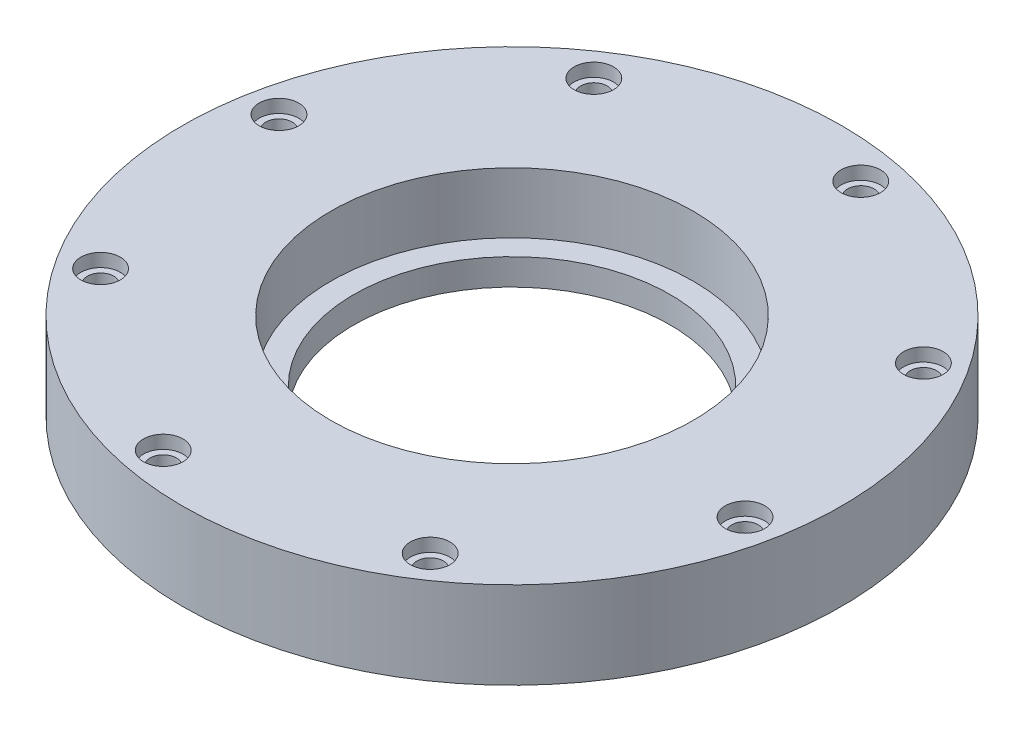
SolidWorks part; units mm, degrees
ref_plane "Front Plane" through (0, 0, 0) normal (0, 0, 1) x (1, 0, 0)
ref_plane "Top Plane" through (0, 0, 0) normal (0, 1, 0) x (1, 0, 0)
ref_plane "Right Plane" through (0, 0, 0) normal (1, 0, 0) x (0, 0, -1)
sketch "Sketch1" plane through (0, 0, 0) normal (0, 1, 0) x (1, 0, 0)
  circle A0 centre (0, 0) radius 24
  circle A1 centre (0, 0) radius 50
  dimension "D1" = 100
  dimension "D2" = 48
extrude "Boss-Extrude1" add sketch "Sketch1" along normal blind 13.2
sketch "Sketch2" plane through (0, 13.2, 0) normal (0, 1, 0) x (1, 0, 0)
  line L0 (0, 0) -> (24.7487, 24.7487)
  line L1 (0, 0) -> (32.3358, 13.3939)
  line L2 (24.7487, 24.7487) -> (32.3358, 13.3939)
  line L3 (0, 0) -> (28.5423, 19.0713)
  line L4 (28.5423, 19.0713) -> (37.4161, 25.0007)
  circle A0 centre (0, 0) radius 35
  circle A1 centre (0, 35) radius 3
  circle A2 centre (13.3939, 32.3358) radius 3
  circle A3 centre (24.7487, 24.7487) radius 3
  circle A4 centre (32.3358, 13.3939) radius 3
  circle A5 centre (35, 0) radius 3
  circle A6 centre (32.3358, -13.3939) radius 3
  circle A7 centre (24.7487, -24.7487) radius 3
  circle A8 centre (13.3939, -32.3358) radius 3
  circle A9 centre (0, -35) radius 3
  circle A10 centre (-13.3939, -32.3358) radius 3
  circle A11 centre (-24.7487, -24.7487) radius 3
  circle A12 centre (-32.3358, -13.3939) radius 3
  circle A13 centre (-35, 0) radius 3
  circle A14 centre (-32.3358, 13.3939) radius 3
  circle A15 centre (-24.7487, 24.7487) radius 3
  circle A16 centre (-13.3939, 32.3358) radius 3
  arc A17 (24.7487, 24.7487) -> (32.3358, 13.3939) centre (0, 0) cw
  circle A18 centre (0, 0) radius 45
  arc A19 (24.7487, 24.7487) -> (32.3358, 13.3939) centre (0, 0) ccw
  arc A20 (24.7487, 24.7487) -> (32.3358, 13.3939) centre (0, 0) ccw
  circle A21 centre (37.4161, 25.0007) radius 2
  circle A22 centre (44.1353, -8.7791) radius 2
  circle A23 centre (25.0007, -37.4161) radius 2
  circle A24 centre (-8.7791, -44.1353) radius 2
  circle A25 centre (-37.4161, -25.0007) radius 2
  circle A26 centre (-44.1353, 8.7791) radius 2
  circle A27 centre (-25.0007, 37.4161) radius 2
  circle A28 centre (8.7791, 44.1353) radius 2
  circle A29 centre (37.4161, 25.0007) radius 3
  circle A30 centre (44.1353, -8.7791) radius 3
  circle A31 centre (25.0007, -37.4161) radius 3
  circle A32 centre (-8.7791, -44.1353) radius 3
  circle A33 centre (-37.4161, -25.0007) radius 3
  circle A34 centre (-44.1353, 8.7791) radius 3
  circle A35 centre (-25.0007, 37.4161) radius 3
  circle A36 centre (8.7791, 44.1353) radius 3
  point P14 (0, 0)
  point P50 (0, 0)
  point P69 (0, 0)
  dimension "D1" = 70
  dimension "D4" = 90
  dimension "D5" = 4
  dimension "D7" = 6
  dimension "D3" = 16
  dimension "D6" = 8
  dimension "D8" = 8
extrude "Cut-Extrude3" cut sketch "Sketch2" against normal blind 13.2 contours A21
extrude "Cut-Extrude4" cut sketch "Sketch2<6>" against normal blind 2 contours A29
sketch "Sketch2<6>" plane through (0, 13.2, 0) normal (0, 1, 0) x (1, 0, 0) same geometry as "Sketch2"
pattern_circular "CirPattern2" count 8 every 45 about axis through (0, 13.2, 0) along (0, 1, 0) of "Cut-Extrude3"
pattern_circular "CirPattern3" count 8 every 45 about axis through (0, 13.2, 0) along (0, 1, 0) of "Cut-Extrude4"
sketch "Sketch3" plane through (0, 0, 0) normal (0, -1, 0) x (1, 0, 0)
  circle A0 centre (0, 0) radius 35
  circle A1 centre (0, 35) radius 2.75
  dimension "D1" = 70
  dimension "D2" = 5.5
extrude "Cut-Extrude5" cut sketch "Sketch3" against normal blind 4.2 contours A1
pattern_circular "CirPattern4" count 16 every 22.5 about axis through (0, 0, 0) along (0, 1, 0) of "Cut-Extrude5"
sketch "Sketch5" plane through (0, 13.2, 0) normal (0, 1, 0) x (1, 0, 0)
  circle A0 centre (0, 0) radius 27.5
  circle A1 centre (0, 0) radius 27.7
  circle A2 centre (0, 0) radius 21
  circle M10 centre (0, 0) radius 24
  dimension "D1" = 55
extrude "Cut-Extrude9" cut sketch "Sketch5" against normal blind 9.2 contours A0 M10 region at (-26.7222, 13.2, 0)
equation "\"OD\"=100"
equation "\"D1@Sketch1\"=\"OD\""
equation "\"ID_BOTTOM\"= 48"
equation "\"D2@Sketch1\"=\"ID_BOTTOM\""
equation "\"WIDTH\"= 13.2"
equation "\"D1@Boss-Extrude1\"=\"WIDTH\""
equation "\"D_SUN\"=70"
equation "\"D1@Sketch2\"=\"D_SUN\""
equation "\"G_RATIO\"=15"
equation "\"D3@Sketch2\"=\"G_RATIO\"+1"
equation "\"D_PIN\"=6"
equation "\"D2@Sketch2\"=\"D_PIN\""
equation "\"SCREW_D\"=90"
equation "\"D_SCREW\"=90"
equation "\"D4@Sketch2\"=\"D_SCREW\""
equation "\"SCREW\"= 4"
equation "\"D5@Sketch2\"=\"SCREW\""
equation "\"SCREW_NUM\"=8"
equation "\"D6@Sketch2\"=\"SCREW_NUM\""
equation "\"D_TOP_SCREW\"=6"
equation "\"D8@Sketch2\"=\"SCREW_NUM\""
equation "\"D1@Cut-Extrude3\"=\"WIDTH\""
equation "\"SCREW_HEAD_WIDTH\"=2"
equation "\"D1@Cut-Extrude4\"=\"SCREW_HEAD_WIDTH\""
equation "\"R_SUN\"=70"
equation "\"D1@Sketch3\"=\"R_SUN\""
equation "\"D_PIN_HOLE\"=5.5"
equation "\"D2@Sketch3\"=\"D_PIN_HOLE\""
equation "\"HOLE_DEPTH\"= 4.2"
equation "\"D1@Cut-Extrude5\"=\"HOLE_DEPTH\""
equation "\"D1@CirPattern4\"=\"G_RATIO\"+1"
equation "\"BEAR_TOL\"= 0.2"
equation "\"TOP_THICK\"= 2.4"
equation "\"HOLDDIAM\"=42"
equation "\"D_BEAR\"=55"
equation "\"D1@Sketch5\"=\"D_BEAR\""
equation "\"D2@Sketch5\"=\"BEAR_TOL\""
equation "\"D1@Cut-Extrude9\"=\"BEAR_THICK\""
equation "\"BEAR_THICK\"= 9.2"
